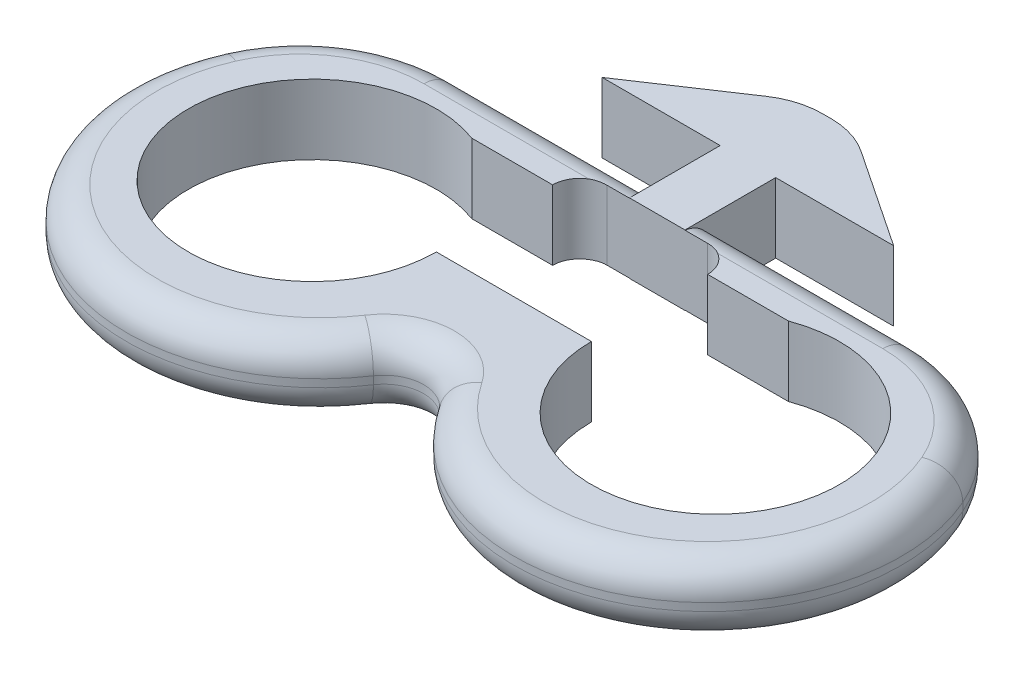
SolidWorks part; units mm, degrees
ref_plane "Front" through (0, 0, 0) normal (0, 0, 1) x (1, 0, 0)
ref_plane "Top" through (0, 0, 0) normal (0, 1, 0) x (1, 0, 0)
ref_plane "Right" through (0, 0, 0) normal (1, 0, 0) x (0, 0, -1)
sketch "Sketch1" plane through (0, 0, 0) normal (0, 1, 0) x (1, 0, 0)
  line L0 (-1.7907, 2.05) -> (-9.398, 2.05)
  line L2 (-1.7907, -2.05) -> (-1.7907, 2.05)
  line L4 (1.7907, -2.05) -> (1.7907, 2.05)
  line L7 (-9.398, 2.05) -> (-1.7907, 7.13)
  line L8 (-1.7907, 7.13) -> (1.7907, 7.13)
  line L9 (1.7907, 7.13) -> (9.398, 2.05)
  line L10 (9.398, 2.05) -> (1.7907, 2.05)
  line L11 (1.7907, -2.05) -> (25.0063, -2.05)
  line L12 (-1.7907, -2.05) -> (-25.0063, -2.05)
  line L13 (-25.0063, -2.05) -> (-25.0063, -13.0482)
  line L14 (-25.0063, -13.0482) -> (25.0063, -13.0482)
  line L15 (25.0063, -13.0482) -> (25.0063, -2.05)
  line L16 (25.0063, -2.05) -> (1.7907, -2.05)
  point P0 (0, 0)
  point P17 (0, 7.13)
  point P19 (0, -13.0482)
  point P24 (1.7907, 0)
  dimension "D1" = 18.796
  dimension "D2" = 3.5814
  dimension "D3" = 50.0126
  dimension "D4" = 10.9982
  dimension "D5" = 5.08
  dimension "D7" = 4.1
extrude "Boss-Extrude1" add sketch "Sketch1" along normal blind 4.5 contours L14 L15 L11 L4 L10 L9 L8 L7 L0 L2 L12 L13 region at (0, 0, 6.3134)
sketch "Sketch3" plane through (0, 4.5, 0) normal (0, 1, 0) x (1, 0, 0)
  line L3 (-25.0063, -13.0482) -> (25.0063, -13.0482) construction
  line L16 (-25.0063, -13.0482) -> (25.0063, -13.0482)
  line L17 (25.0063, -13.0482) -> (25.0063, -2.05)
  line L18 (25.0063, -2.05) -> (1.7907, -2.05)
  line L19 (1.7907, -2.05) -> (1.7907, 2.05)
  line L20 (1.7907, 2.05) -> (9.398, 2.05)
  line L21 (9.398, 2.05) -> (1.7907, 7.13)
  line L22 (1.7907, 7.13) -> (-1.7907, 7.13)
  line L23 (-1.7907, 7.13) -> (-9.398, 2.05)
  line L24 (-9.398, 2.05) -> (-1.7907, 2.05)
  line L25 (-1.7907, 2.05) -> (-1.7907, -2.05)
  line L26 (-1.7907, -2.05) -> (-25.0063, -2.05)
  line L27 (-25.0063, -2.05) -> (-25.0063, -13.0482)
  line L28 (-25.0063, -13.0482) -> (25.0063, -13.0482)
  arc A2 (-25.0063, -13.0482) -> (-2.1111, -20.0005) centre (-12.5031, -13.0482) ccw
  arc A3 (2.1111, -20.0005) -> (25.0063, -13.0482) centre (12.5032, -13.0482) ccw
  arc A4 (2.1111, -20.0005) -> (-2.1111, -20.0005) centre (0, -21.4129) ccw
  point P14 (0, -13.0482)
  line M15 (-25.0063, -13.0482) -> (25.0063, -13.0482)
  dimension "D2" = 2.54
  dimension "D1" = 0
extrude "Boss-Extrude2" add sketch "Sketch3" against normal up to surface (4.5 mm away) contours A2 M15 | L28 A3 region at (0, 4.5, 18.3456) up to face at (0, 0, 0.9864)
sketch "Sketch4" plane through (0, 4.5, 0) normal (0, 1, 0) x (1, 0, 0)
  line L0 (-1025.0063, -13.0482) -> (48974.9937, -13.0482) construction
  circle A0 centre (-13, -13.0482) radius 8
  circle A1 centre (13, -13.0482) radius 8
  dimension "D1" = 16
  dimension "D2" = 13
  dimension "D3" = 13
extrude "Cut-Extrude2" cut sketch "Sketch4" against normal through all
sketch "Sketch5" plane through (0, 4.5, 0) normal (0, 1, 0) x (1, 0, 0)
  line L2 (-3.25, -5.55) -> (3.25, -5.55) construction
  line L3 (-3.25, -3.8) -> (3.25, -3.8)
  line L5 (1.7907, -2.05) -> (25.0063, -2.05) construction
  line L8 (-5, -5.55) -> (-10.2113, -5.55)
  line L9 (5, -5.55) -> (10.2113, -5.55)
  line L10 (-5, -13.0482) -> (5, -13.0482)
  circle A0 centre (-13, -13.0482) radius 8 construction
  circle A1 centre (13, -13.0482) radius 8 construction
  arc A3 (-3.25, -3.8) -> (-5, -5.55) centre (-3.25, -5.55) ccw
  arc A4 (5, -5.55) -> (3.25, -3.8) centre (3.25, -5.55) ccw
  arc A8 (10.2113, -5.55) -> (5, -13.0482) centre (13, -13.0482) ccw
  arc A9 (-5, -13.0482) -> (-10.2113, -5.55) centre (-13, -13.0482) ccw
  point P7 (0, -5.55)
  point P12 (0, -15.5882)
  point P28 (0, -10.5082)
  dimension "D3" = 2.54
  dimension "D5" = 1.75
  dimension "D10" = 2.54
extrude "Cut-Extrude4" cut sketch "Sketch5" against normal up to next contours L8 A9 L10 A8 L9 A4 L3 A3
sketch "Sketch6" plane through (0, 4.5, 0) normal (0, 1, 0) x (1, 0, 0)
  line L0 (-18.4503, -2.05) -> (-25.0063, -2.05)
  line L1 (-25.0063, -2.05) -> (-25.0063, -13.0482)
  line L2 (-1.7907, -2.05) -> (-25.0063, -2.05) construction
  line L3 (25.0063, -13.0482) -> (25.0063, -2.05)
  line L4 (25.0063, -2.05) -> (18.4503, -2.05)
  arc A0 (-18.4503, -2.05) -> (-25.0063, -13.0482) centre (-12.5031, -13.0482) ccw
  arc A1 (-25.0063, -13.0482) -> (-2.1111, -20.0005) centre (-12.5031, -13.0482) ccw construction
  arc A2 (25.0063, -13.0482) -> (18.4503, -2.05) centre (12.5032, -13.0482) ccw
  arc A3 (2.1111, -20.0005) -> (25.0063, -13.0482) centre (12.5032, -13.0482) ccw construction
extrude "Cut-Extrude5" cut sketch "Sketch6" against normal up to next
fillet "Fillet1" radius 10 1 edges at (-18.4503, 2.25, 2.05)
fillet "Fillet2" radius 10 1 edges at (18.4503, 2.25, 2.05)
fillet "Fillet3" radius 5 2 edges at (-1.7907, 2.25, -7.13) (1.7907, 2.25, -7.13)
fillet "Fillet4" radius 2 14 edges at (-8.2947, 4.5, 2.05) (-20.2815, 4.5, 3.6871) (8.2947, 4.5, 2.05) (20.2815, 4.5, 3.6871) (18.4964, 4.5, 24.0213) (0, 4.5, 18.8729) (8.2947, 0, 2.05) (20.2815, 0, 3.6871) (18.4964, 0, 24.0213) (0, 0, 18.8729) (-8.2947, 0, 2.05) (-20.2815, 0, 3.6871) (-18.4964, 4.5, 24.0213) (-18.4964, 0, 24.0213)
ref_plane "Plane1" through (-5, 0, 13.0482) normal (-1, 0, 0) x (0, 0, 1)
